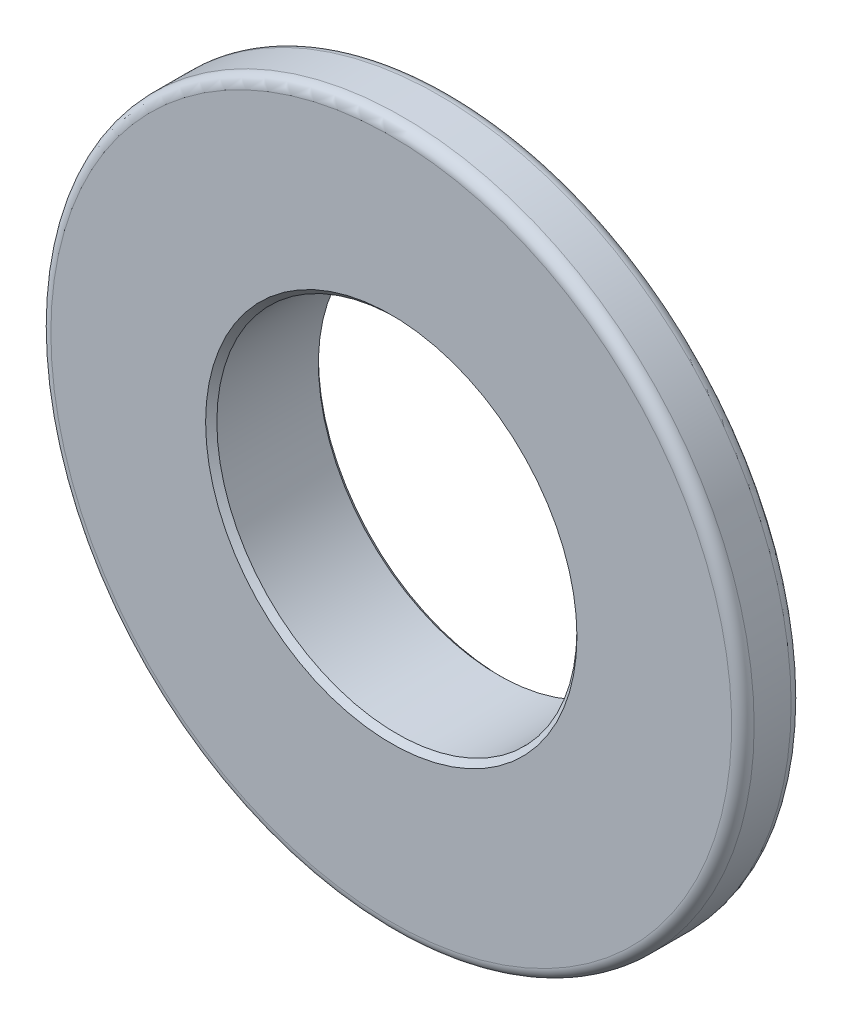
SolidWorks part; units mm, degrees
note: '?' marks a value the reader was unsure of.
ref_plane "front" through (0, 0, 0) normal (0, 0, 1) x (1, 0, 0)
ref_plane "top" through (0, 0, 0) normal (0, 1, 0) x (1, 0, 0)
ref_plane "right" through (0, 0, 0) normal (1, 0, 0) x (0, 0, -1)
ref_axis "Axis1" through (0, 0, -22.5998) along (0, 0, -1)?
sketch "Sketch1" plane through (0, 0, 0) normal (1, 0, 0) x (0, 0, -1)
  line L0 (32.131, 15.875) -> (32.131, 8.128)
  line L1 (32.131, 8.128) -> (37.2229, 8.128)
  line L2 (32.131, 15.875) -> (34.6352, 15.875)
  line L3 (0, 0) -> (38.1, 0) construction
  arc A0 (37.2229, 8.128) -> (34.6352, 15.875) centre (0, 0) ccw
  dimension "D1" = 38.1
  dimension "D2" = 16.256
  dimension "D3" = 31.75
  dimension "D4" = 32.131
  dimension "D5" = 2.5042
  dimension "D6" = 5.969
  dimension "D7" = 5.0919
revolve "Revolve1" add sketch "Sketch1" angle 360 about L3
chamfer "Chamfer1" distance 0.254 angle 45 2 edges at (8.128, 0, -37.2229) (8.128, 0, -32.131)
fillet "Fillet1" radius 0.508 2 edges at (15.875, 0, -34.6352) (15.875, 0, -32.131)
